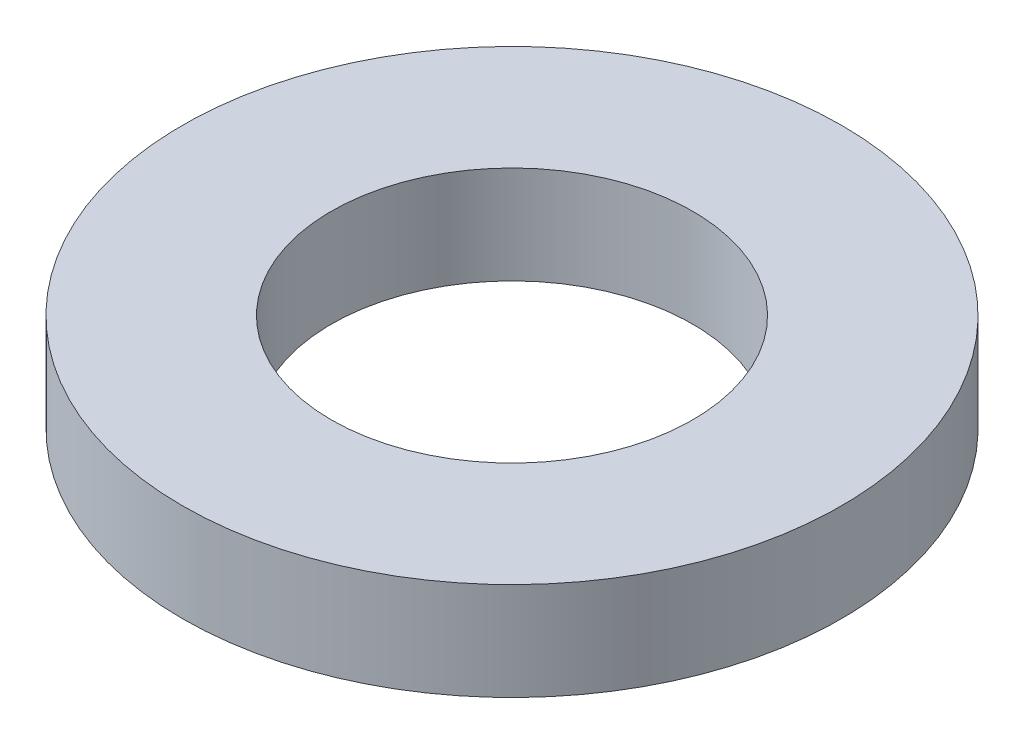
SolidWorks part; units mm, degrees
ref_plane "Front Plane" through (0, 0, 0) normal (0, 0, 1) x (1, 0, 0)
ref_plane "Top Plane" through (0, 0, 0) normal (0, 1, 0) x (1, 0, 0)
ref_plane "Right Plane" through (0, 0, 0) normal (1, 0, 0) x (0, 0, -1)
sketch "Sketch1" plane through (0, 0, 0) normal (0, 1, 0) x (1, 0, 0)
  circle A0 centre (0, 0) radius 77.5
  dimension "FLANGE_OD" = 155
extrude "Boss-Extrude1" add sketch "Sketch1" along normal blind 23
sketch "Sketch2" plane through (0, 0, 0) normal (0, 1, 0) x (1, 0, 0)
  circle A0 centre (0, 0) radius 42.5
  dimension "BORE_D" = 85
extrude "Cut-Extrude1" cut sketch "Sketch2" along normal through all
sketch "Sketch3" plane through (0, 23, 0) normal (0, 1, 0) x (1, 0, 0)
  circle A0 centre (0, 0) radius 31.727 construction
  circle A1 centre (-31.727, 0) radius 3.7722
  dimension "BOLT_D" = 7.5444
  dimension "BOLT_PCD" = 63.454
extrude "Cut-Extrude2" cut sketch "Sketch3" against normal blind 20.0048 rebuild error yes
pattern_circular "CirPattern1" count 8 over 360 rebuild error yes
